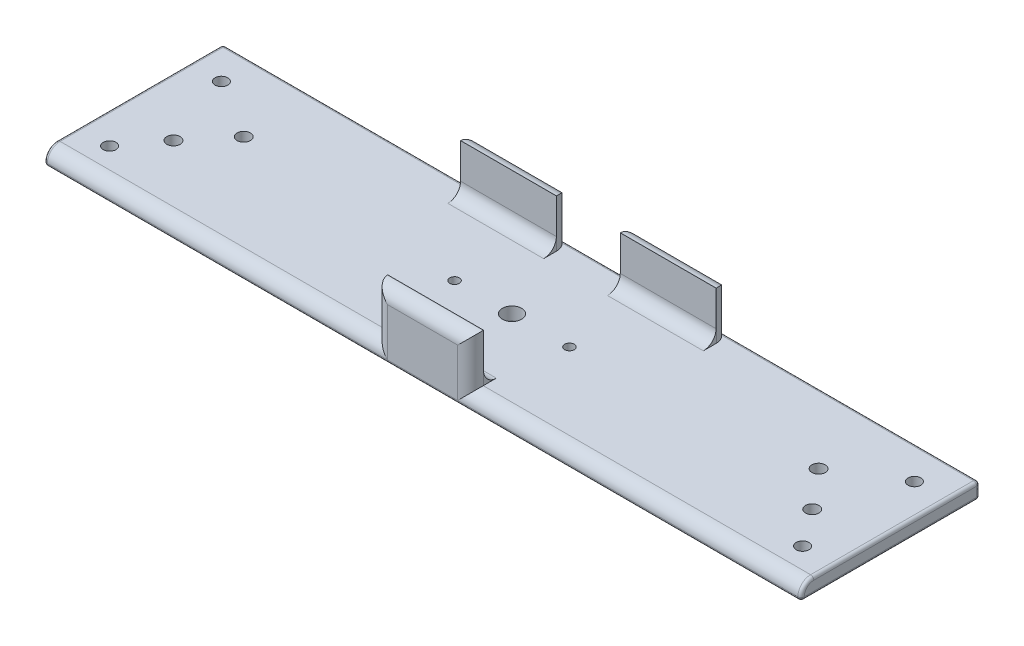
SolidWorks part; units mm, degrees
ref_plane "Front Plane" through (0, 0, 0) normal (0, 0, 1) x (1, 0, 0)
ref_plane "Top Plane" through (0, 0, 0) normal (0, 1, 0) x (1, 0, 0)
ref_plane "Right Plane" through (0, 0, 0) normal (1, 0, 0) x (0, 0, -1)
sketch "Sketch1" plane through (0, 0, 0) normal (0, 1, 0) x (1, 0, 0)
  line L1 (-118.5, -28) -> (118.5, -28)
  line L2 (-118.5, -28) -> (-118.5, 28)
  line L3 (-118.5, 28) -> (118.5, 28)
  line L4 (118.5, -28) -> (118.5, 28)
  line L5 (-118.5, -28) -> (118.5, 28) construction
  line L6 (-118.5, 28) -> (118.5, -28) construction
  point P0 (0, 0)
  dimension "D1" = 237
  dimension "D2" = 56
extrude "Boss-Extrude1" add sketch "Sketch1" along normal blind 5
sketch "Sketch2" plane through (0, 0, 0) normal (0, -1, 0) x (1, 0, 0)
  line L0 (0, 28) -> (0, -28) construction
  line L1 (-118.5, 28) -> (118.5, 28) construction
  line L2 (118.5, -28) -> (-118.5, -28) construction
  line L3 (118.5, 28) -> (118.5, -28) construction
  line L4 (0, 0) -> (-68.3657, 0) construction
  circle A0 centre (-18, 0) radius 1.5
  circle A1 centre (18, 0) radius 1.5
  circle A2 centre (0, 0) radius 3
  circle A3 centre (108.5, 18) radius 2
  circle A4 centre (108.5, -7) radius 2
  circle A5 centre (-108.5, -7) radius 2
  circle A6 centre (-108.5, 18) radius 2
  dimension "D1" = 3
  dimension "D2" = 18
  dimension "D4" = 6
  dimension "D5" = 4
  dimension "D6" = 10
  dimension "D7" = 10
  dimension "D9" = 25
  dimension "D8" = 2
extrude "Cut-Extrude1" cut sketch "Sketch2" against normal blind 5
sketch "Sketch5" plane through (0, 5, 0) normal (0, 1, 0) x (1, 0, 0)
  line L0 (0, -28) -> (0, -23.9) construction
  line L1 (-118.5, -28) -> (118.5, -28) construction
  line L2 (-15, -23.9) -> (15, -23.9)
  line L3 (-15, -23.9) -> (-15, -28)
  line L4 (-15, -28) -> (15, -28)
  line L5 (15, -28) -> (15, -23.9)
  line L6 (-118.5, 0) -> (118.5, 0) construction
  line L7 (-118.5, 28) -> (-118.5, -28) construction
  line L8 (118.5, -28) -> (118.5, 28) construction
  line L9 (0, 28) -> (0, 23.9) construction
  line L14 (40, 28) -> (40, 23.9)
  line L15 (-10, 28) -> (-40, 28)
  line L16 (-10, 28) -> (-10, 23.9)
  line L17 (-10, 23.9) -> (-40, 23.9)
  line L18 (-40, 28) -> (-40, 23.9)
  line L23 (10, 23.9) -> (40, 23.9)
  line L24 (10, 28) -> (10, 23.9)
  line L25 (10, 28) -> (40, 28)
  line L26 (0, 0) -> (0, -23.9) construction
  line L27 (-25, 23.9) -> (-25, 0) construction
  line L28 (25, 23.9) -> (25, 0) construction
  point P8 (0, -23.9)
  point P22 (0, 23.9)
  dimension "D1" = 30
  dimension "D2" = 4.1
  dimension "D3" = 10
  dimension "D4" = 4.1
  dimension "D5" = 30
extrude "Boss-Extrude2" add sketch "Sketch5" along normal blind 15
fillet "Fillet1" radius 4 11 edges at (-66.75, 5, 28) (-15, 12.5, 28) (0, 20, 28) (15, 12.5, 28) (66.75, 5, 28) (40, 12.5, -28) (25, 20, -28) (-10, 12.5, -28) (10, 12.5, -28) (-40, 12.5, -28) (-25, 20, -28)
fillet "Fillet3" radius 4 3 edges at (0, 5, 23.9) (25, 5, -23.9) (-25, 5, -23.9)
fillet "Fillet8" radius 1 16 edges at (0, 0, 28) (-18, 0, -1.5) (18, 0, 1.5) (0, 0, -3) (118.5, 0, 0) (118.5, 3.8284, 26.8284) (118.5, 5, -2) (0, 5, -28) (-77.25, 5, -28) (0, 0, -28) (118.5, 2.5, -28) (77.25, 5, -28) (-118.5, 0, 0) (-118.5, 2.5, -28) (-118.5, 5, -2) (-118.5, 3.8284, 26.8284)
sketch "Sketch14" plane through (0, 0, 0) normal (0, -1, 0) x (1, 0, 0)
  line L0 (-117.5, 0) -> (117.5, 0) construction
  line L1 (117.5, -27) -> (117.5, 27) construction
  line L2 (0, 0) -> (0, 27) construction
  line L3 (117.5, 27) -> (-117.5, 27) construction
  line L4 (-118.5, -27) -> (-118.5, 27) construction
  circle A0 centre (-108.5, 17.5) radius 2
  circle A1 centre (-108.5, -17.5) radius 2
  circle A2 centre (108.5, -17.5) radius 2
  circle A3 centre (108.5, 17.5) radius 2
  point P9 (0, 0)
  dimension "D1" = 4
  dimension "D2" = 17.5
  dimension "D3" = 10
extrude "Cut-Extrude6" cut sketch "Sketch14" against normal blind 60
sketch "Sketch15" plane through (0, 5, 0) normal (0, 1, 0) x (1, 0, 0)
  line L0 (0, 0) -> (0, 27) construction
  line L1 (11.3542, 27) -> (-11.3542, 27) construction
  line L2 (-117.5, 0) -> (117.5, 0) construction
  line L3 (117.5, -24) -> (117.5, 27) construction
  circle A2 centre (-90, 6) radius 2.1
  circle A6 centre (-100, -6) radius 2.1
  circle A7 centre (100, -6) radius 2.1
  circle A8 centre (90, 6) radius 2.1
  point P13 (0, 0)
  dimension "D1" = 4.2
  dimension "D2" = 6
  dimension "D3" = 90
  dimension "D4" = 4.2
  dimension "D5" = 6
  dimension "D6" = 10
extrude "Cut-Extrude7" cut sketch "Sketch15" against normal blind 60
